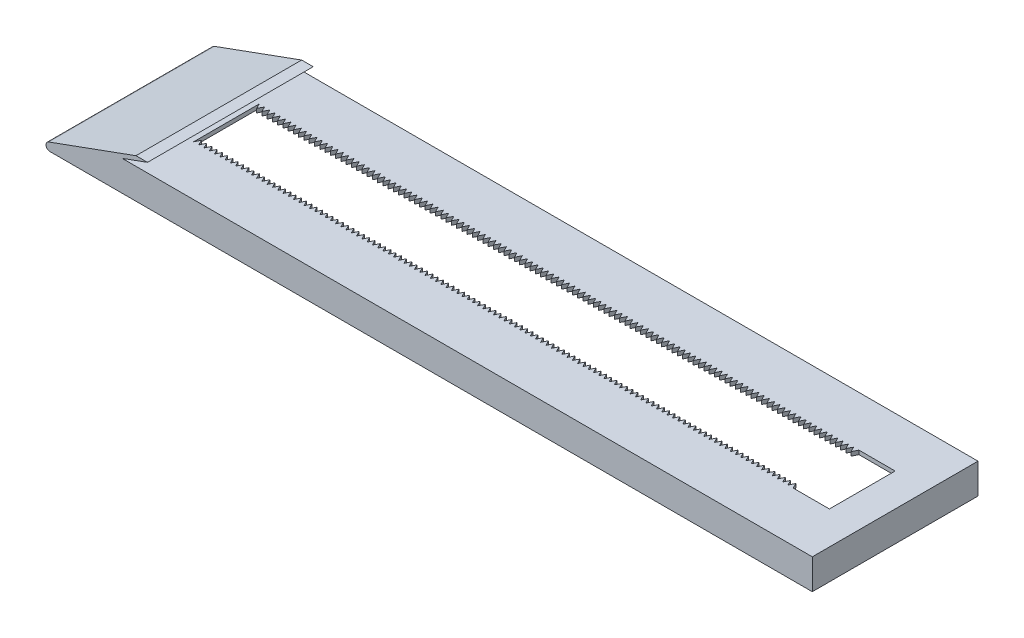
SolidWorks part; units mm, degrees
material "1060 Alloy"
ref_plane "Front Plane" through (0, 0, 0) normal (0, 0, 1) x (1, 0, 0)
ref_plane "Top Plane" through (0, 0, 0) normal (0, 1, 0) x (1, 0, 0)
ref_plane "Right Plane" through (0, 0, 0) normal (1, 0, 0) x (0, 0, -1)
sketch "Sketch1" plane through (0, 0, 0) normal (0, 0, 1) x (1, 0, 0)
  line L0 (0, 0) -> (530.529, 0)
  line L1 (530.529, 0) -> (530.529, -3)
  line L2 (530.529, -3) -> (0.529, -3)
  line L3 (0.529, -3) -> (-46.1781, -20)
  line L4 (-46.1781, -20) -> (-33.192, -20)
  line L5 (-33.192, -20) -> (-33.192, -23)
  line L6 (-33.192, -23) -> (-63.192, -23)
  line L7 (-63.192, -23) -> (0, 0)
  dimension "D1" = 3
  dimension "D2" = 3
  dimension "D3" = 3
  dimension "D4" = 530
  dimension "D5" = 160
  dimension "D6" = 30
  dimension "D7" = 20
extrude "Boss-Extrude1" add sketch "Sketch1" along normal blind 120
sketch "Sketch2" plane through (0, 0, 120) normal (0, 0, 1) x (1, 0, 0)
  line L0 (530.529, 0) -> (0, 0)
  line L1 (0, 0) -> (-63.192, -23)
  line L2 (-63.192, -23) -> (530.529, -23)
  line L3 (530.529, -23) -> (530.529, 0)
extrude "Boss-Extrude2" add sketch "Sketch2" along normal blind 3
sketch "Sketch3" plane through (0, 0, 0) normal (0, 0, -1) x (-1, 0, 0)
  line L0 (-530.529, 0) -> (0, 0)
  line L1 (0, 0) -> (63.192, -23)
  line L2 (63.192, -23) -> (-530.529, -23)
  line L3 (-530.529, -23) -> (-530.529, 0)
extrude "Boss-Extrude3" add sketch "Sketch3" along normal blind 3
sketch "Sketch4" plane through (530.529, 0, 0) normal (1, 0, 0) x (0, 0, -1)
  line L0 (-123, 0) -> (3, 0)
  line L1 (3, 0) -> (3, -23)
  line L2 (3, -23) -> (-123, -23)
  line L3 (-123, -23) -> (-123, 0)
extrude "Boss-Extrude4" add sketch "Sketch4" along normal blind 3
sketch "Sketch5" plane through (0, 0, 0) normal (0, 1, 0) x (1, 0, 0)
  line L0 (533.529, 3) -> (533.529, -123) construction
  line L1 (25, -85) -> (508.529, -85)
  line L2 (25, -85) -> (25, -35)
  line L3 (25, -35) -> (508.529, -35)
  line L4 (508.529, -85) -> (508.529, -35)
  line L5 (25, -85) -> (508.529, -35) construction
  line L6 (25, -35) -> (508.529, -85) construction
  line L7 (0, -123) -> (0, 3) construction
  line L8 (533.529, -60) -> (0, -60) construction
  point P0 (266.7645, -60)
  point P11 (0, 0)
  dimension "D1" = 25
  dimension "D2" = 50
  dimension "D3" = 25
extrude "Cut-Extrude1" cut sketch "Sketch5" against normal blind 3
sketch "Sketch6" plane through (0, 0, 0) normal (0, 1, 0) x (1, 0, 0)
  line L0 (25, -35) -> (27, -39)
  line L1 (27, -39) -> (29, -35)
  line L2 (508.529, -35) -> (25, -35) construction
  line L3 (27, -39) -> (27, -34.5086) construction
  line L8 (508.529, -35) -> (25, -35)
  line L9 (508.529, -85) -> (508.529, -35)
  line L10 (25, -85) -> (508.529, -85)
  line L11 (25, -35) -> (25, -85)
  line L12 (29, -35) -> (25, -35)
  dimension "D1" = 2
  dimension "D2" = 2
  dimension "D3" = 4
  dimension "D4" = 0
extrude "Boss-Extrude5" add sketch "Sketch6" against normal blind 3
pattern_linear "LPattern1" count 114 spacing 4 along (1, 0, 0) of "Boss-Extrude5"
sketch "Sketch7" plane through (0, 0, 0) normal (0, 1, 0) x (1, 0, 0)
  line L0 (25, -60) -> (508.529, -60) construction
  line L1 (25, -35) -> (25, -85) construction
  line L2 (508.529, -85) -> (508.529, -35) construction
ref_plane "Plane1" through (0, 0, 60) normal (0, 0, 1) x (1, 0, 0)
mirror "Mirror1" about plane through (0, 0, 60) normal (0, 0, 1) of "Boss-Extrude5", "LPattern1"
sketch "Sketch8" plane through (0, 0, 123) normal (0, 0, 1) x (1, 0, 0)
  line L0 (0, 0) -> (19.2323, 7)
  line L1 (19.2323, 7) -> (28.0038, 7)
  line L2 (28.0038, 7) -> (8.7714, 0)
  line L3 (533.529, 0) -> (0, 0) construction
  line L4 (0, 0) -> (-63.192, -23) construction
  line L5 (0, 0) -> (8.7714, 0)
  dimension "D1" = 7
  dimension "D2" = 3
extrude "Boss-Extrude6" add sketch "Sketch8" against normal blind 126
fillet "Fillet1" radius 3 1 edges at (-63.192, -23, 60)
